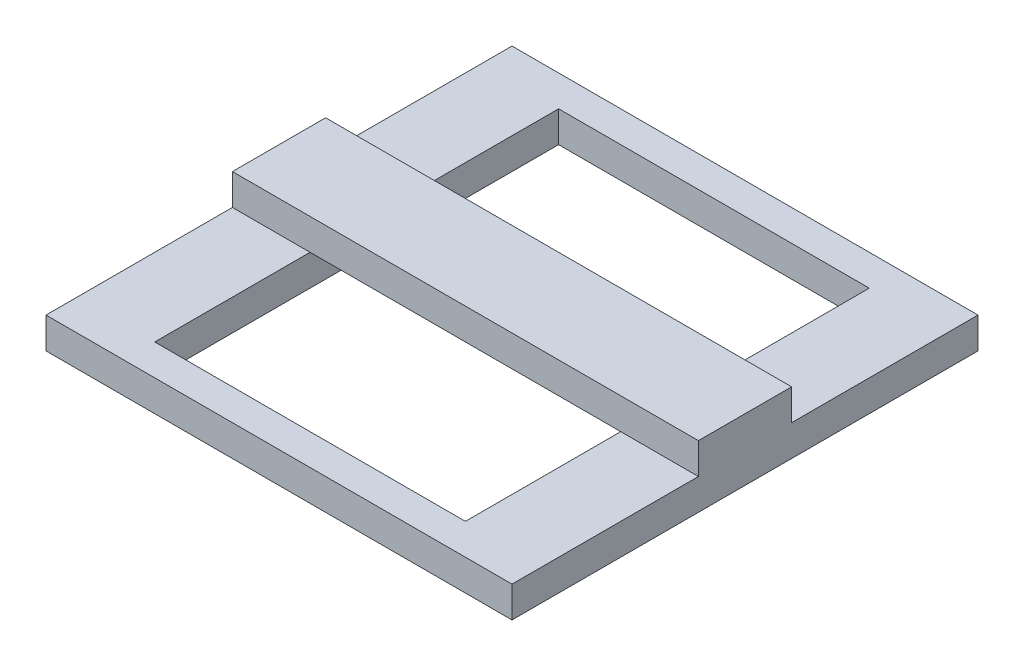
SolidWorks part; units mm, degrees
ref_plane "Front Plane" through (0, 0, 0) normal (0, 0, 1) x (1, 0, 0)
ref_plane "Top Plane" through (0, 0, 0) normal (0, 1, 0) x (1, 0, 0)
ref_plane "Right Plane" through (0, 0, 0) normal (1, 0, 0) x (0, 0, -1)
sketch "Sketch1" plane through (0, 0, 0) normal (0, 1, 0) x (1, 0, 0)
  line L1 (0, 0) -> (-150, 0)
  line L2 (0, 0) -> (0, 30)
  line L3 (0, 30) -> (-150, 30)
  line L4 (-150, 0) -> (-150, 30)
  dimension "D1" = 30
  dimension "D2" = 150
extrude "Boss-Extrude1" add sketch "Sketch1" along normal blind 10
sketch "Sketch8" plane through (0, 0, 0) normal (0, -1, 0) x (-1, 0, 0)
  line L0 (150, 0) -> (0, 30)
  line L1 (150, 30) -> (0, 0)
  line L2 (150, 0) -> (0, 0) construction
sketch "Sketch9" plane through (0, 0, 0) normal (0, -1, 0) x (1, 0, 0)
  line L0 (-150, -30) -> (0, 0) construction
  line L1 (0, -90) -> (-150, -90)
  line L2 (0, -90) -> (0, 60)
  line L3 (0, 60) -> (-150, 60)
  line L4 (-150, -90) -> (-150, 60)
  line L5 (0, -90) -> (-150, 60) construction
  line L6 (0, 60) -> (-150, -90) construction
  line L8 (-125, -80) -> (-25, -80)
  line L9 (-125, -80) -> (-125, 50)
  line L10 (-125, 50) -> (-25, 50)
  line L11 (-25, -80) -> (-25, 50)
  line L12 (-125, -80) -> (-25, 50) construction
  line L13 (-125, 50) -> (-25, -80) construction
  point P0 (-75, -15)
  point P7 (-75, -15)
  dimension "D1" = 150
  dimension "D2" = 150
  dimension "D3" = 130
  dimension "D4" = 100
extrude "Boss-Extrude3" add sketch "Sketch9" along normal blind 10
